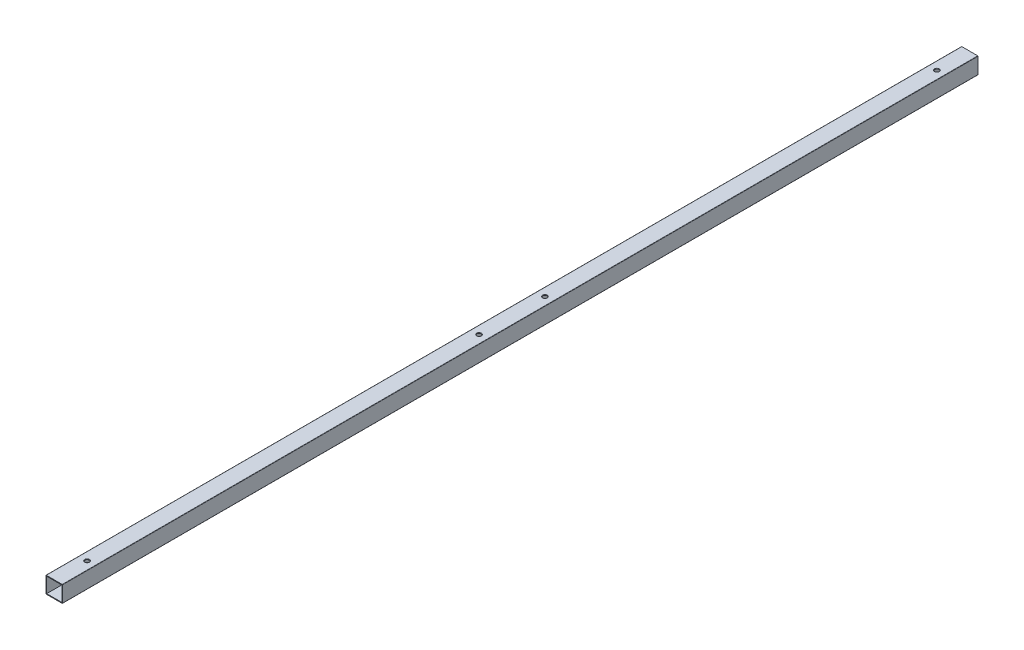
SolidWorks part; units mm, degrees
material "Plain Carbon Steel"
ref_plane "Front Plane" through (0, 0, 0) normal (0, 0, 1) x (1, 0, 0)
ref_plane "Top Plane" through (0, 0, 0) normal (0, 1, 0) x (1, 0, 0)
ref_plane "Right Plane" through (0, 0, 0) normal (1, 0, 0) x (0, 0, -1)
sketch "Sketch2" plane through (0, 0, 0) normal (0, 0, 1) x (1, 0, 0)
  line L0 (0, 19.05) -> (1.5875, 19.05) construction
  line L1 (0, 0) -> (38.1, 0)
  line L2 (0, 0) -> (0, 38.1)
  line L3 (0, 38.1) -> (38.1, 38.1)
  line L4 (38.1, 0) -> (38.1, 38.1)
  line L5 (1.5875, 1.5875) -> (36.5125, 1.5875)
  line L6 (1.5875, 1.5875) -> (1.5875, 36.5125)
  line L7 (1.5875, 36.5125) -> (36.5125, 36.5125)
  line L8 (36.5125, 1.5875) -> (36.5125, 36.5125)
  line L9 (19.05, 36.5125) -> (19.05, 38.1) construction
  line L10 (36.5125, 19.05) -> (38.1, 19.05) construction
  line L11 (19.05, 0) -> (19.05, 1.5875) construction
  dimension "D1" = 38.1
  dimension "D2" = 1.5875
  dimension "D3" = 38.1
extrude "Boss-Extrude1" add sketch "Sketch2" along normal blind 2120.9
hole_wizard "X (0.397) Diameter Hole1" positions "Sketch4" profile "Sketch3" hole size "X" standard "ANSI Inch" end condition through all
sketch "Sketch4" plane through (0, 0, 0) normal (0, -1, 0) x (-1, 0, 0)
  line L0 (-19.05, -2120.9) -> (-19.05, -2044.7) construction
  line L1 (0, -2120.9) -> (-38.1, -2120.9) construction
  line L2 (-19.05, -2044.7) -> (-19.05, -1136.65) construction
  line L3 (-19.05, -1136.65) -> (-19.05, -984.25) construction
  line L4 (-19.05, -984.25) -> (-19.05, -76.2) construction
  line L5 (-19.05, -76.2) -> (-19.05, 0) construction
  line L6 (0, 0) -> (-38.1, 0) construction
  point P0 (-19.05, -2044.7)
  point P2 (-19.05, -1136.65)
  point P4 (-19.05, -984.25)
  point P6 (-19.05, -76.2)
  dimension "D1" = 76.2
  dimension "D2" = 152.4
sketch "Sketch3" plane through (19.05, 0, 2044.7) normal (1, 0, 0) x (0, 0, -1)
  line L0 (0, 0) -> (0, 38.1)
  line L1 (0, 38.1) -> (5.0419, 38.1)
  line L2 (5.0419, 38.1) -> (5.0419, 0)
  line L5 (5.0419, 0) -> (0, 0)
  line L11 (0, -6.35) -> (0, 107.95) construction
  dimension "Thru Hole Dia." = 10.0838
  dimension "Thru Hole Depth" = 38.1
fillet "Fillet3" radius 0.635 20 edges at (19.05, 38.1, 71.1581) (19.05, 36.5125, 71.1581) (19.05, 0, 71.1581) (19.05, 1.5875, 81.2419) (19.05, 38.1, 979.2081) (19.05, 36.5125, 979.2081) (19.05, 0, 979.2081) (19.05, 1.5875, 989.2919) (19.05, 38.1, 1131.6081) (19.05, 36.5125, 1131.6081) (19.05, 0, 1131.6081) (19.05, 1.5875, 1141.6919) (19.05, 38.1, 2039.6581) (19.05, 36.5125, 2039.6581) (19.05, 0, 2039.6581) (19.05, 1.5875, 2049.7419) (38.1, 0, 1060.45) (0, 0, 1060.45) (38.1, 38.1, 1060.45) (0, 38.1, 1060.45)
